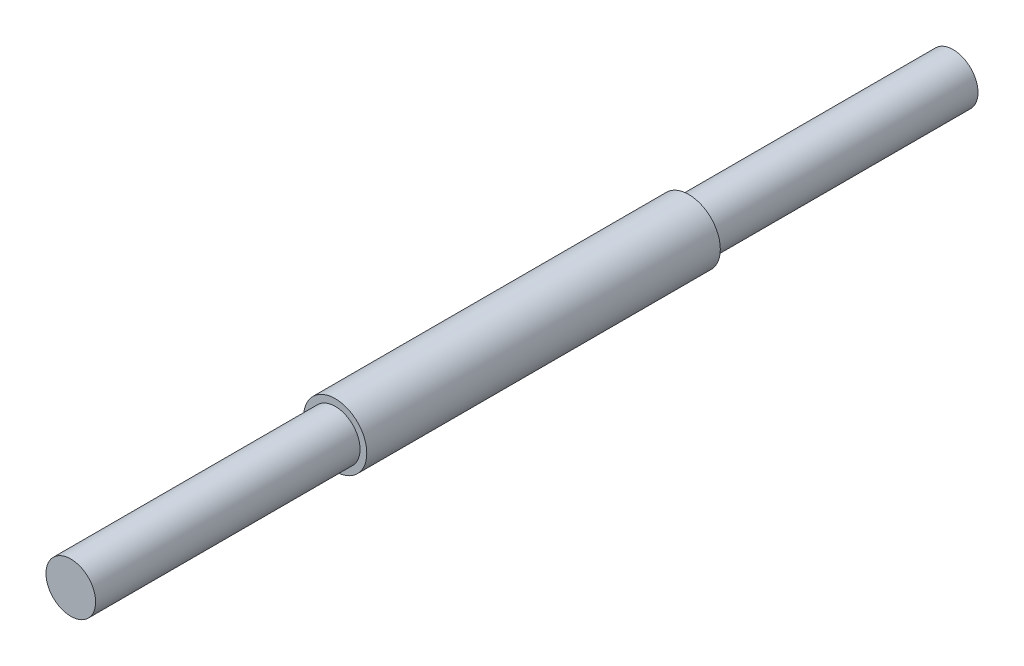
SolidWorks part; units mm, degrees
ref_plane "Front Plane" through (0, 0, 0) normal (0, 0, 1) x (1, 0, 0)
ref_plane "Top Plane" through (0, 0, 0) normal (0, 1, 0) x (1, 0, 0)
ref_plane "Right Plane" through (0, 0, 0) normal (1, 0, 0) x (0, 0, -1)
sketch "Sketch2" plane through (0, 0, 0) normal (0, 0, 1) x (1, 0, 0)
  circle A0 centre (0, 0) radius 2.5
  dimension "D1" = 5
extrude "Boss-Extrude1" add sketch "Sketch2" along normal blind 44.3738 and the other way blind 44.3738
sketch "Sketch3" plane through (0, 0, 0) normal (0, 0, 1) x (1, 0, 0)
  circle A0 centre (0, 0) radius 3.175
  dimension "D1" = 6.35
extrude "Boss-Extrude2" add sketch "Sketch3" along normal blind 17.78 and the other way blind 17.78
